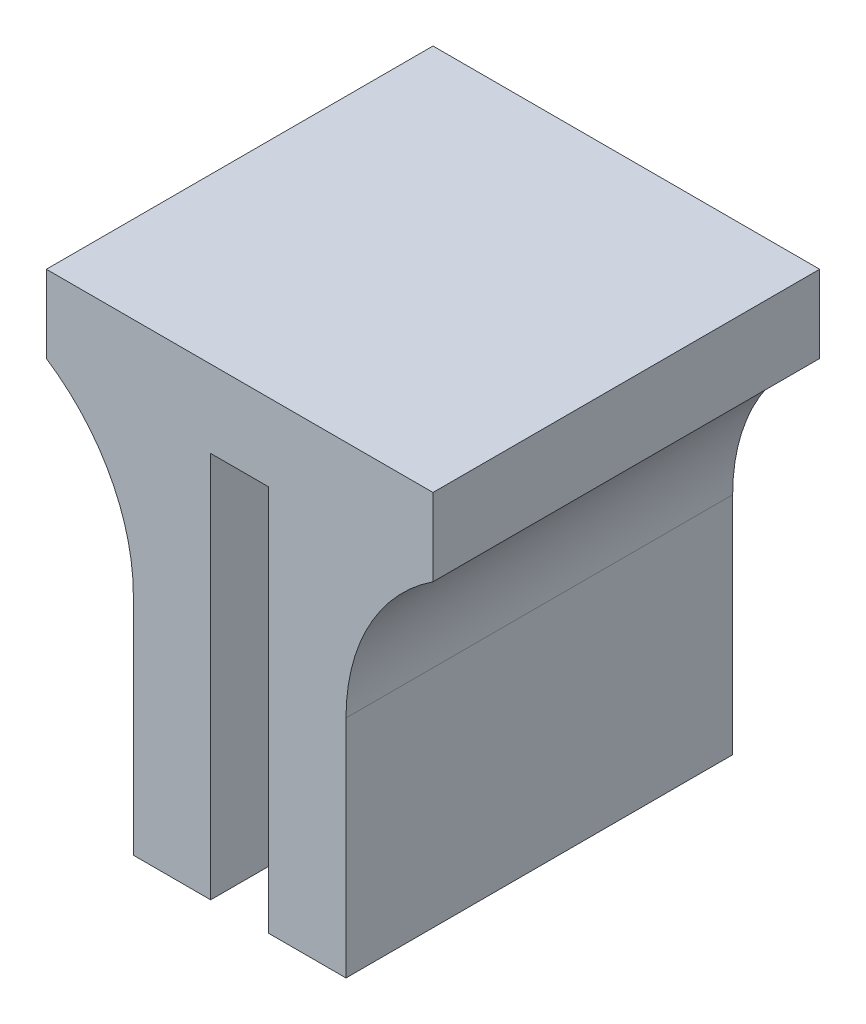
SolidWorks part; units mm, degrees
ref_plane "Front" through (0, 0, 0) normal (0, 0, 1) x (1, 0, 0)
ref_plane "Top" through (0, 0, 0) normal (0, 1, 0) x (1, 0, 0)
ref_plane "Right" through (0, 0, 0) normal (1, 0, 0) x (0, 0, -1)
sketch "Sketch1" plane through (0, 0, 0) normal (0, 0, 1) x (1, 0, 0)
  line L0 (0, 0) -> (0, 20)
  line L1 (0, 20) -> (3, 20)
  line L2 (3, 20) -> (3, 0)
  line L3 (3, 0) -> (7, 0)
  line L4 (7, 0) -> (7, 20)
  line L5 (7, 20) -> (11.5, 20)
  line L6 (11.5, 20) -> (11.5, 24)
  line L7 (11.5, 24) -> (-8.5, 24)
  line L8 (-8.5, 24) -> (-8.5, 20)
  line L9 (-4, 0) -> (0, 0)
  line L10 (-8.5, 20) -> (-4, 20)
  line L11 (-4, 20) -> (-4, 0)
  line L12 (1.5, 20) -> (1.5, 0) construction
  point P15 (0, 0)
  dimension "D1" = 3
  dimension "D2" = 4
  dimension "D3" = 20
  dimension "D4" = 20
  dimension "D5" = 4
extrude "Boss-Extrude1" add sketch "Sketch1" along normal blind 20
fillet "Fillet1" radius 10 2 edges at (-4, 20, 10) (7, 20, 10)
